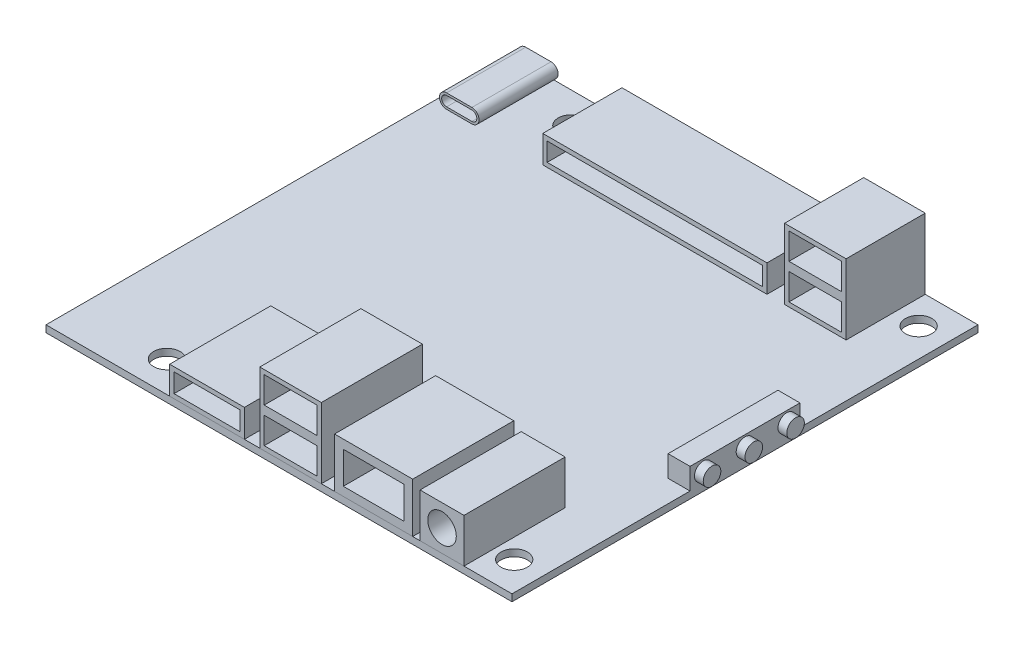
SolidWorks part; units mm, degrees
material "Copper"
ref_plane "Front Plane" through (0, 0, 0) normal (0, 0, 1) x (1, 0, 0)
ref_plane "Top Plane" through (0, 0, 0) normal (0, 1, 0) x (1, 0, 0)
ref_plane "Right Plane" through (0, 0, 0) normal (1, 0, 0) x (0, 0, -1)
sketch "Sketch1" plane through (0, 0, 0) normal (0, 1, 0) x (1, 0, 0)
  line L0 (0, 0) -> (-53, 0) construction
  line L1 (-53, -53) -> (53, -53)
  line L2 (-53, -53) -> (-53, 53)
  line L3 (-53, 53) -> (53, 53)
  line L4 (53, -53) -> (53, 53)
  line L5 (-53, -53) -> (53, 53) construction
  line L6 (-53, 53) -> (53, -53) construction
  line L7 (0, 0) -> (0, 53) construction
  circle A0 centre (46.5, -46) radius 3
  circle A1 centre (-32.5, -46) radius 3
  circle A2 centre (-32.5, 46) radius 3
  circle A3 centre (46.5, 46) radius 3
  point P0 (0, 0)
  dimension "D3" = 79
  dimension "D4" = 92
  dimension "D5" = 6
  dimension "D6" = 92
  dimension "D7" = 79
  dimension "D9" = 7
  dimension "D1" = 106
  dimension "D2" = 106
  dimension "D8" = 6.5
extrude "Boss-Extrude1" add sketch "Sketch1" along normal blind 1.57
sketch "Sketch2" plane through (0, 0, 53) normal (0, 0, 1) x (1, 0, 0)
  line L0 (-53, 1.57) -> (53, 1.57) construction
  line L1 (-24.87, 1.57) -> (-7.87, 1.57)
  line L2 (-24.87, 1.57) -> (-24.87, 7.87)
  line L3 (-24.87, 7.87) -> (-7.87, 7.87)
  line L4 (-7.87, 1.57) -> (-7.87, 7.87)
  line L5 (-53, 1.57) -> (-53, 0) construction
  line L6 (-4.37, 1.57) -> (9.63, 1.57)
  line L7 (-4.37, 1.57) -> (-4.37, 9.57)
  line L8 (-4.37, 9.57) -> (9.63, 9.57)
  line L9 (9.63, 1.57) -> (9.63, 9.57)
  line L10 (-4.37, 9.57) -> (9.63, 9.57)
  line L11 (-4.37, 9.57) -> (-4.37, 17.57)
  line L12 (-4.37, 17.57) -> (9.63, 17.57)
  line L13 (9.63, 9.57) -> (9.63, 17.57)
  line L14 (12.63, 1.57) -> (30.41, 1.57)
  line L15 (12.63, 1.57) -> (12.63, 12.87)
  line L16 (12.63, 12.87) -> (30.41, 12.87)
  line L17 (30.41, 1.57) -> (30.41, 12.87)
  line L18 (32.08, 1.57) -> (42.08, 1.57)
  line L19 (32.08, 1.57) -> (32.08, 11.57)
  line L20 (32.08, 11.57) -> (42.08, 11.57)
  line L21 (42.08, 1.57) -> (42.08, 11.57)
  line L38 (-23.87, 2.57) -> (-23.87, 6.87)
  line L39 (-23.87, 6.87) -> (-8.87, 6.87)
  line L40 (-8.87, 2.57) -> (-8.87, 6.87)
  line L41 (-23.87, 2.57) -> (-8.87, 2.57)
  line L42 (14.63, 3.57) -> (14.63, 10.87)
  line L43 (-3.37, 8.57) -> (8.63, 8.57)
  line L44 (-3.37, 8.57) -> (-3.37, 2.57)
  line L45 (-3.37, 2.57) -> (8.63, 2.57)
  line L46 (8.63, 8.57) -> (8.63, 2.57)
  line L47 (-3.37, 16.57) -> (8.63, 16.57)
  line L48 (-3.37, 16.57) -> (-3.37, 10.57)
  line L49 (-3.37, 10.57) -> (8.63, 10.57)
  line L50 (8.63, 16.57) -> (8.63, 10.57)
  line L51 (14.63, 10.87) -> (28.41, 10.87)
  line L52 (28.41, 3.57) -> (28.41, 10.87)
  line L53 (14.63, 3.57) -> (28.41, 3.57)
  circle A0 centre (37.08, 6.57) radius 3.25
  point P34 (2.63, 16.57)
  point P38 (2.63, 17.57)
  point P43 (8.63, 13.57)
  point P45 (9.63, 13.57)
  point P46 (8.63, 5.57)
  point P47 (9.63, 5.57)
  point P48 (2.63, 8.57)
  point P49 (2.63, 9.57)
  point P52 (37.08, 11.57)
  point P54 (32.08, 6.57)
  line M51 (53, 1.57) -> (-53, 1.57)
  dimension "D17" = 6.5
  dimension "D1" = 17
  dimension "D2" = 6.3
  dimension "D3" = 28.13
  dimension "D5" = 3.5
  dimension "D6" = 16
  dimension "D7" = 14
  dimension "D8" = 1
  dimension "D9" = 1
  dimension "D10" = 3
  dimension "D11" = 11.3
  dimension "D12" = 17.78
  dimension "D14" = 1.67
  dimension "D15" = 10
  dimension "D16" = 10
  dimension "D4" = 1
  dimension "D13" = 2
extrude "Boss-Extrude2" add sketch "Sketch2" against normal blind 23 separate body contours L4 L3 L2 L41 L38 L39 L40 M51 | L9 L8 L7 L43 L46 L45 L44 M51 | L8 L13 L12 L11 L47 L50 L49 L48 | L17 L16 L15 L53 L42 L51 L52 M51 | L21 L20 L19 A0 M51 region at (-24.6887, 4.72, 53) region at (32.2214, 6.57, 53) region at (12.8407, 7.22, 53) region at (-4.2088, 5.57, 53) region at (-4.2088, 13.57, 53)
sketch "Sketch3" plane through (0, 0, -53) normal (0, 0, -1) x (-1, 0, 0)
  line L0 (-53, 1.57) -> (53, 1.57) construction
  line L1 (-41, 1.57) -> (-27, 1.57)
  line L2 (-41, 1.57) -> (-41, 9.57)
  line L3 (-41, 9.57) -> (-27, 9.57)
  line L4 (-27, 1.57) -> (-27, 9.57)
  line L5 (-30.41, 1.57) -> (-12.63, 1.57) construction
  line L6 (-41, 9.57) -> (-27, 9.57)
  line L7 (-41, 9.57) -> (-41, 17.57)
  line L8 (-41, 17.57) -> (-27, 17.57)
  line L9 (-27, 9.57) -> (-27, 17.57)
  line L10 (-40, 16.57) -> (-28, 16.57)
  line L11 (-40, 16.57) -> (-40, 10.57)
  line L12 (-40, 10.57) -> (-28, 10.57)
  line L13 (-28, 16.57) -> (-28, 10.57)
  line L14 (-40, 8.57) -> (-28, 8.57)
  line L15 (-40, 8.57) -> (-40, 2.57)
  line L16 (-40, 2.57) -> (-28, 2.57)
  line L17 (-28, 8.57) -> (-28, 2.57)
  line L18 (-53, 1.57) -> (-53, 0) construction
  line L19 (44.125, 3.195) -> (49.875, 3.195) construction
  line L20 (-23, 1.57) -> (28, 1.57)
  line L21 (-23, 1.57) -> (-23, 7.77)
  line L22 (-23, 7.77) -> (28, 7.77)
  line L23 (28, 1.57) -> (28, 7.77)
  line L24 (-22, 6.77) -> (27, 6.77)
  line L25 (-22, 6.77) -> (-22, 2.57)
  line L26 (-22, 2.57) -> (27, 2.57)
  line L27 (27, 6.77) -> (27, 2.57)
  line L28 (44.125, 4.82) -> (49.875, 4.82)
  line L29 (44.125, 1.57) -> (49.875, 1.57)
  line L30 (53, 1.57) -> (53, 0) construction
  line L31 (44.125, 4.32) -> (49.875, 4.32)
  line L32 (44.125, 2.07) -> (49.875, 2.07)
  arc A0 (44.125, 4.82) -> (44.125, 1.57) centre (44.125, 3.195) ccw
  arc A1 (49.875, 1.57) -> (49.875, 4.82) centre (49.875, 3.195) ccw
  arc A2 (49.875, 2.07) -> (49.875, 4.32) centre (49.875, 3.195) ccw
  arc A3 (44.125, 4.32) -> (44.125, 2.07) centre (44.125, 3.195) ccw
  point P18 (-34, 16.57)
  point P19 (-34, 17.57)
  point P20 (-40, 13.57)
  point P21 (-41, 13.57)
  point P22 (-40, 5.57)
  point P23 (-41, 5.57)
  point P24 (-34, 8.57)
  point P25 (-34, 9.57)
  point P36 (2.5, 6.77)
  point P37 (2.5, 7.77)
  point P38 (-22, 4.67)
  point P39 (-23, 4.67)
  point P42 (47, 3.195)
  line M35 (53, 1.57) -> (-53, 1.57)
  dimension "D12" = 9
  dimension "D13" = 1.5
  dimension "D1" = 16
  dimension "D2" = 14
  dimension "D3" = 12
  dimension "D4" = 1
  dimension "D5" = 1
  dimension "D6" = 51
  dimension "D7" = 1
  dimension "D8" = 1
  dimension "D9" = 4
  dimension "D10" = 6.2
  dimension "D11" = 3.25
  dimension "D14" = 0.5
extrude "Boss-Extrude3" add sketch "Sketch3" against normal blind 18 separate body contours L4 L3 L2 L14 L17 L16 L15 M35 | L3 L9 L8 L7 L10 L13 L12 L11 | L23 L22 L21 L24 L27 L26 L25 M35 | A1 L28 A0 A3 L31 A2 L32 M35 region at (40.8388, 5.57, -53) region at (-42.5957, 3.195, -53) region at (22.4862, 4.67, -53) region at (40.8388, 13.57, -53)
sketch "Sketch4" plane through (53, 0, 0) normal (1, 0, 0) x (0, 0, -1)
  line L0 (-9.5, 4) -> (9.5, 4) construction
  line L1 (-53, 0) -> (53, 0) construction
  line L2 (-53, 1.57) -> (53, 1.57) construction
  line L3 (-12.5, 1.57) -> (12.5, 1.57)
  line L4 (-12.5, 1.57) -> (-12.5, 6.43)
  line L5 (-12.5, 6.43) -> (12.5, 6.43)
  line L6 (12.5, 1.57) -> (12.5, 6.43)
  line L7 (-12.5, 1.57) -> (12.5, 6.43) construction
  line L8 (-12.5, 6.43) -> (12.5, 1.57) construction
  circle A0 centre (-9.5, 4) radius 2
  circle A1 centre (0, 4) radius 2
  circle A2 centre (9.5, 4) radius 2
  line M11 (53, 1.57) -> (-53, 1.57)
  dimension "D1" = 23
  dimension "D2" = 4
  dimension "D3" = 6
  dimension "D4" = 25
extrude "Boss-Extrude4" add sketch "Sketch4" against normal blind 5 contours A0 | A1 | L6 L5 L4 A2 A1 A0 M11 | A2 region at (53, 4, 12.2453) region at (53, 4, 9.5) region at (53, 4, 0) region at (53, 4, -9.5)
extrude "Boss-Extrude5" add sketch "Sketch4<3>" along normal blind 2 contours A0 | A1 | A2 region at (53, 4, 9.5) region at (53, 4, 0) region at (53, 4, -9.5)
sketch "Sketch4<3>" plane through (53, 0, 0) normal (1, 0, 0) x (0, 0, -1) same geometry as "Sketch4"
